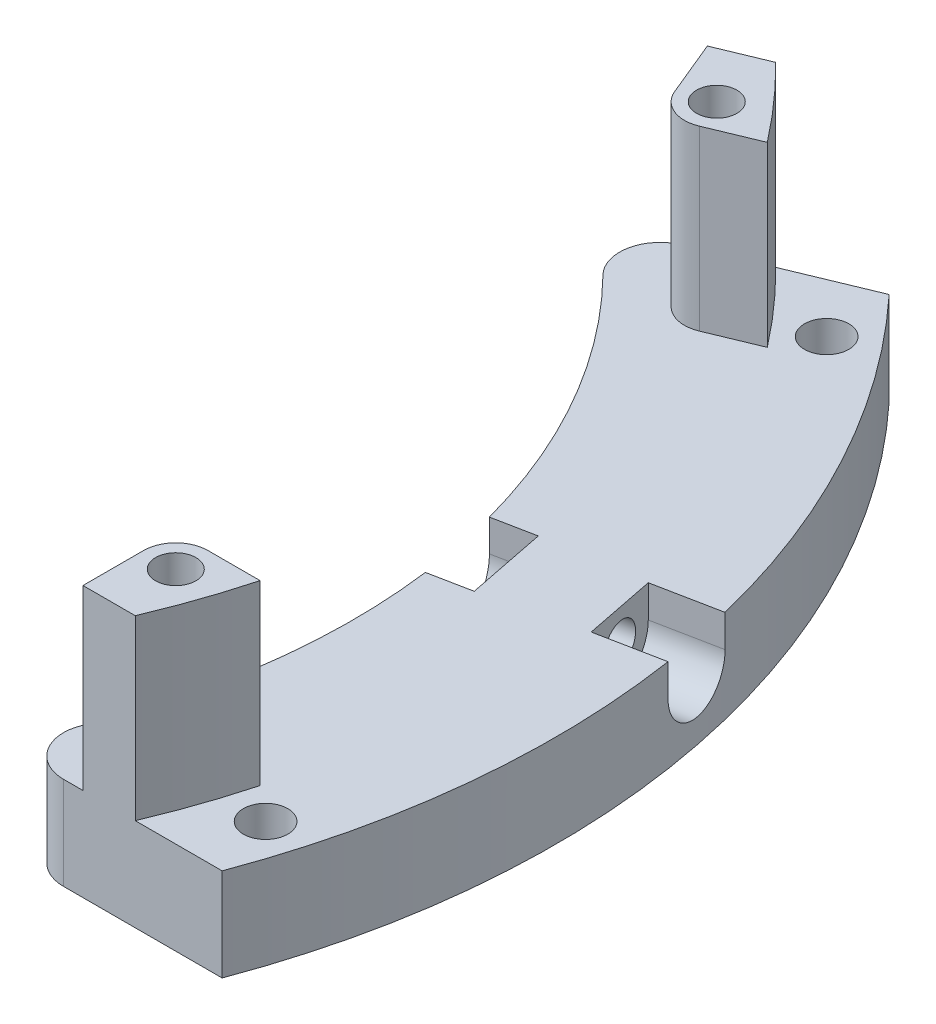
SolidWorks part; units mm, degrees
ref_plane "Front Plane" through (0, 0, 0) normal (0, 0, 1) x (1, 0, 0)
ref_plane "Top Plane" through (0, 0, 0) normal (0, 1, 0) x (1, 0, 0)
ref_plane "Right Plane" through (0, 0, 0) normal (1, 0, 0) x (0, 0, -1)
sketch "Sketch1" plane through (0, 0, 0) normal (0, 1, 0) x (1, 0, 0)
  line L0 (66.175, -35) -> (93.675, -35)
  line L1 (47.7438, 57.6598) -> (73.1505, 68.1836)
  line L2 (0, -35) -> (66.175, -35) construction
  line L3 (-13.3939, 32.3358) -> (47.7438, 57.6598) construction
  arc A0 (73.1505, 68.1836) -> (93.675, -35) centre (0, 0) cw
  arc A1 (47.7438, 57.6598) -> (66.175, -35) centre (0, 0) cw
  circle A2 centre (0, 0) radius 35 construction
  dimension "D1" = 100
  dimension "D3" = 27.5
  dimension "D4" = 70
  dimension "D2" = 22.5
extrude "Boss-Extrude1" add sketch "Sketch1" along normal blind 11.5
sketch "Sketch2" plane through (0, 11.5, 0) normal (0, -1, 0) x (1, 0, 0)
  line L0 (66.175, 35) -> (93.675, 35) construction
  line L1 (73.1505, -68.1836) -> (47.7438, -57.6598) construction
  line L2 (73.1505, -68.1836) -> (47.7438, -57.6598) construction
  line L3 (80.4285, 23.5) -> (86.8778, 23.5)
  line L4 (76.4285, 27.5) -> (76.4285, 35)
  line L5 (66.175, 35) -> (93.675, 35) construction
  line L6 (76.4285, 35) -> (82.9156, 35)
  line L7 (60.087, -54.6546) -> (57.2168, -61.5837)
  line L8 (65.3132, -52.4898) -> (71.2715, -54.9579)
  line L9 (63.2101, -64.0662) -> (57.2168, -61.5837)
  arc A0 (82.9156, 35) -> (63.2101, -64.0662) centre (0, 0) cw construction
  arc A1 (73.1505, -68.1836) -> (93.675, 35) centre (0, 0) ccw construction
  arc A2 (76.4285, 27.5) -> (80.4285, 23.5) centre (80.4285, 27.5) ccw
  circle A3 centre (80.4285, 27.5) radius 5 construction
  arc A4 (65.3132, -52.4898) -> (60.087, -54.6546) centre (63.7825, -56.1854) ccw
  circle A5 centre (63.7825, -56.1854) radius 5 construction
  arc A6 (82.9156, 35) -> (86.8778, 23.5) centre (0, 0) cw
  arc A7 (63.2101, -64.0662) -> (71.2715, -54.9579) centre (0, 0) ccw
  dimension "D1" = 10
  dimension "D2" = 10
  dimension "D4" = 8
  dimension "D5" = 7.5
  dimension "D3" = 7.5
extrude "Boss-Extrude2" add sketch "Sketch2" against normal offset from surface (22 mm away) 22
sketch "Sketch3" plane through (0, 33.5, 0) normal (0, 1, 0) x (1, 0, 0)
  circle A0 centre (63.7825, 56.1854) radius 2.5
  circle A1 centre (80.4285, -27.5) radius 2.5
  dimension "D1" = 5
extrude "Cut-Extrude1" cut sketch "Sketch3" against normal blind 4
sketch "Sketch4" plane through (0, 0, 0) normal (0, -1, 0) x (1, 0, 0)
  circle A0 centre (91.0607, 27) radius 4.5
  circle A1 centre (73.7967, -59.7922) radius 4.5
  dimension "D1" = 9
extrude "Cut-Extrude2" cut sketch "Sketch4" against normal blind 5
sketch "Sketch5" plane through (0, 5, 0) normal (0, -1, 0) x (1, 0, 0)
  circle A0 centre (91.0607, 27) radius 2.75
  circle A1 centre (73.7967, -59.7922) radius 2.75
  dimension "D1" = 5.5
extrude "Cut-Extrude3" cut sketch "Sketch5" against normal through all
ref_plane "Plane1" through (56.9594, 0, -11.3299) normal (-0.9808, 0, 0.1951) x (0.1951, 0, 0.9808)
sketch "Sketch6" plane through (56.9594, 0, -11.3299) normal (-0.9808, 0, 0.1951) x (0.1951, 0, 0.9808)
  line L1 (47.2376, 11.5) -> (-47.2376, 11.5) construction
  circle A0 centre (0, 7.5) radius 5 construction
  circle A1 centre (0, 7.5) radius 2.5
  circle A2 centre (0, 7.5) radius 4.5 construction
  dimension "D1" = 10
  dimension "D2" = 4
  dimension "D3" = 5
  dimension "D4" = 9
extrude "Cut-Extrude4" cut sketch "Sketch6" against normal through all
ref_plane "Plane2" through (98.0785, 0, -19.509) normal (0.9808, 0, -0.1951) x (-0.1951, 0, -0.9808)
ref_plane "Plane3" through (77.519, 0, -15.4195) normal (0.9808, 0, -0.1951) x (-0.1951, 0, -0.9808)
sketch "Sketch8" plane through (98.0785, 0, -19.509) normal (0.9808, 0, -0.1951) x (-0.1951, 0, -0.9808)
  line L0 (-4.5, 7.5) -> (-4.5, 11.5)
  line L1 (52.6026, 11.5) -> (-52.6026, 11.5) construction
  line L2 (4.5, 7.5) -> (4.5, 11.5)
  line L3 (4.5, 11.5) -> (-4.5, 11.5)
  arc A1 (-4.5, 7.5) -> (4.5, 7.5) centre (0, 7.5) ccw
  dimension "D1" = 9
extrude "Cut-Extrude5" cut sketch "Sketch8" against normal blind 8.2
sketch "Sketch7" plane through (0, 11.5, 0) normal (0, 1, 0) x (1, 0, 0)
  line L1 (69.4749, 18.9683) -> (71.4453, 9.0624) construction
  line L2 (0, 0) -> (70.4601, 14.0154) construction
  line L3 (69.4749, 18.9683) -> (93.9945, 23.8456) construction
  line L4 (93.9945, 23.8456) -> (95.9649, 13.9397) construction
  line L5 (95.9649, 13.9397) -> (71.4453, 9.0624) construction
  line L7 (89.1582, 22.3228) -> (90.914, 13.4958) construction
  line L10 (69.4749, 18.9683) -> (71.4453, 9.0624)
  line L11 (71.4453, 9.0624) -> (79.2915, 10.6231)
  line L12 (79.2915, 10.6231) -> (77.3211, 20.5291)
  line L13 (77.3211, 20.5291) -> (69.4749, 18.9683)
  line L14 (89.0906, 22.8701) -> (91.061, 12.9642) construction
  line L16 (66.175, -35) -> (76.4285, -35) construction
  line L17 (57.2168, 61.5837) -> (47.7438, 57.6598) construction
  arc A1 (53.0676, 59.8651) -> (71.9375, -35) centre (0, 0) cw construction
  point P15 (90.0361, 17.9093)
  dimension "D3" = 8
  dimension "D5" = 80
  dimension "D1" = 10.1
  dimension "D2" = 25
  dimension "D4" = 5
extrude "Cut-Extrude6" cut sketch "Sketch7" against normal blind 9
fillet "Fillet1" radius 5.05 2 edges at (76.7659, 2.5, -10.1208) (74.7955, 2.5, -20.0267)
fillet "Fillet2" radius 5 2 edges at (66.175, 5.75, 35) (47.7438, 5.75, -57.6598)
